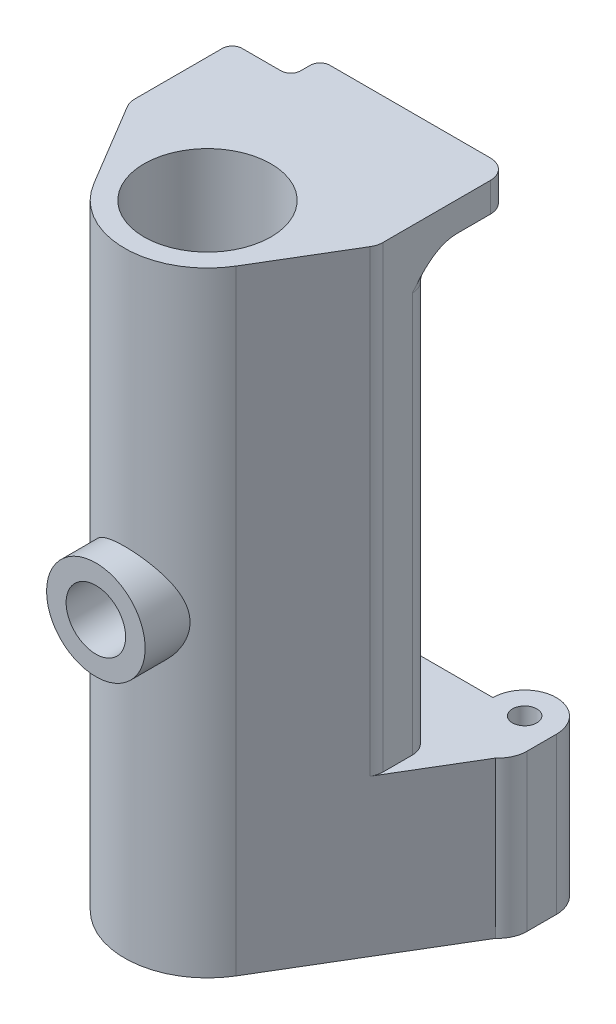
SolidWorks part; units mm, degrees
material "PLA (20%–30% infill + wall)"
ref_plane "Front Plane" through (0, 0, 0) normal (0, 0, 1) x (1, 0, 0)
ref_plane "Top Plane" through (0, 0, 0) normal (0, 1, 0) x (1, 0, 0)
ref_plane "Right Plane" through (0, 0, 0) normal (1, 0, 0) x (0, 0, -1)
sketch "Sketch1" plane through (0, 0, 0) normal (0, 1, 0) x (1, 0, 0)
  line L0 (0, 0) -> (-15, 0) construction
  line L1 (0, 0) -> (0, 18.8352) construction
  line L2 (-11.75, 0) -> (11.75, 0)
  line L3 (-18.25, 0) -> (-18.25, -6)
  line L4 (-18.25, -6) -> (18.25, -6)
  line L5 (18.25, -6) -> (18.25, 0)
  circle A0 centre (-15, 0) radius 1.25
  circle A1 centre (15, 0) radius 1.25
  circle A2 centre (-15, 0) radius 3.25
  circle A3 centre (15, 0) radius 3.25
  dimension "D1" = 30
  dimension "D2" = 2.5
  dimension "D4" = 6
  dimension "D3" = 2
extrude "Boss-Extrude1" add sketch "Sketch1" along normal blind 16 contours A2 A0 | L5 A3 L2 A2 L3 L4 | A3 A1 region at (-15, 0, 3.1581) region at (0, 0, 3.2894) region at (15, 0, -3.1581)
fillet "Fillet1" radius 3 2 edges at (18.25, 8, 6) (-18.25, 8, 6)
sketch "Sketch2" plane through (0, 0, 0) normal (0, -1, 0) x (-1, 0, 0)
  line L0 (0, -6) -> (0, -12.5349) construction
  line L1 (15.25, -6) -> (-15.25, -6) construction
  line L2 (-17.246, -5.2396) -> (-7.2931, -21.8658)
  line L3 (-15.25, -6) -> (15.25, -6)
  line L4 (17.246, -5.2396) -> (7.2931, -21.8658)
  circle A0 centre (0, -17.5) radius 6.5
  arc A1 (-7.2931, -21.8658) -> (7.2931, -21.8658) centre (0, -17.5) ccw
  arc A2 (15.25, -6) -> (18.25, -3) centre (15.25, -3) ccw construction
  arc A3 (-18.25, -3) -> (-15.25, -6) centre (-15.25, -3) ccw construction
  arc A4 (15.25, -6) -> (17.246, -5.2396) centre (15.25, -3) ccw
  arc A5 (-17.246, -5.2396) -> (-15.25, -6) centre (-15.25, -3) ccw
  circle A6 centre (0, -17.5) radius 8.5 construction
  circle M5 centre (15, 0) radius 1.25
  line M6 (-18.25, 0) -> (-18.25, -3)
  arc M7 (-18.25, -3) -> (-15.25, -6) centre (-15.25, -3) ccw
  line M8 (-15.25, -6) -> (15.25, -6)
  arc M9 (15.25, -6) -> (18.25, -3) centre (15.25, -3) ccw
  line M10 (18.25, -3) -> (18.25, 0)
  arc M11 (18.25, 0) -> (11.75, 0) centre (15, 0) ccw
  line M12 (11.75, 0) -> (-11.75, 0)
  arc M13 (-11.75, 0) -> (-18.25, 0) centre (-15, 0) ccw
  circle M14 centre (-15, 0) radius 1.25
  dimension "D1" = 13
  dimension "D3" = 11.5
  dimension "D2" = 2
extrude "Boss-Extrude3" add sketch "Sketch2" against normal blind 10 contours L2 A1 L4 L3 A0 M9 M8 M7 | L3 M13 M6 M7 M8 M9 M10 M11 M12 M14 M5 region at (16.4613, 0, 6.1797) region at (0, 0, 2.4765)
sketch "Sketch3" plane through (0, 10, 0) normal (0, 1, 0) x (1, 0, 0)
  line L2 (-17.246, -5.2396) -> (-7.2931, -21.8658) construction
  line L12 (17.246, -5.2396) -> (7.2931, -21.8658) construction
  line L13 (14.2529, -10.2396) -> (7.2931, -21.8658)
  line L14 (-14.2529, -10.2396) -> (-7.2931, -21.8658)
  line L20 (-14.2529, -10.2396) -> (14.2529, -10.2396)
  line L21 (-15.25, -6) -> (15.25, -6) construction
  circle A1 centre (0, -17.5) radius 6.5 construction
  arc A13 (-7.2931, -21.8658) -> (7.2931, -21.8658) centre (0, -17.5) ccw construction
  circle A15 centre (0, -17.5) radius 6.5
  arc A16 (-7.2931, -21.8658) -> (7.2931, -21.8658) centre (0, -17.5) ccw
  dimension "D1" = 4.2396
extrude "Boss-Extrude4" add sketch "Sketch3" along normal blind 53
fillet "Fillet3" radius 2 2 edges at (14.2529, 36.5, 10.2396) (-14.2529, 36.5, 10.2396)
ref_plane "Plane1" through (0, 0, 18.2396) normal (0, 0, -1) x (-1, 0, 0)
sketch "Sketch4" plane through (0, 0, 18.2396) normal (0, 0, -1) x (-1, 0, 0)
  line L0 (0, 0) -> (0, 63) construction
  line L1 (7.2931, 63) -> (-7.2931, 63) construction
  circle A0 centre (0, 31.5) radius 3.05
  dimension "D1" = 6.1
extrude "Cut-Extrude1" cut sketch "Sketch4" against normal through all
ref_plane "Plane2" through (0, 0, 25.9396) normal (0, 0, -1) x (-1, 0, 0)
sketch "Sketch6" plane through (0, 0, 25.9396) normal (0, 0, -1) x (-1, 0, 0)
  circle A0 centre (0, 31.5) radius 3.05 construction
  circle A1 centre (0, 31.5) radius 3.05
  circle A2 centre (0, 31.5) radius 5.05
  dimension "D1" = 2
extrude "Boss-Extrude5" add sketch "Sketch6" along normal up to surface and the other way blind 3 up to face at (-0.4906, 34.5103, 25.9858)
sketch "Sketch7" plane through (0, 10, 0) normal (0, 1, 0) x (1, 0, 0)
  line L4 (-10.7246, -10.2396) -> (10.7246, -10.2396)
  line L5 (12.4407, -13.2669) -> (17.246, -5.2396)
  line L6 (15.25, -6) -> (-15.25, -6)
  line L7 (-17.246, -5.2396) -> (-12.4407, -13.2669)
  line L8 (-10.7246, -10.2396) -> (10.7246, -10.2396)
  line L9 (12.4407, -13.2669) -> (17.246, -5.2396)
  line L10 (15.25, -6) -> (-15.25, -6)
  line L11 (-17.246, -5.2396) -> (-12.4407, -13.2669)
  arc A4 (12.4407, -13.2669) -> (10.7246, -10.2396) centre (10.7246, -12.2396) ccw
  arc A5 (15.25, -6) -> (17.246, -5.2396) centre (15.25, -3) ccw
  arc A6 (-17.246, -5.2396) -> (-15.25, -6) centre (-15.25, -3) ccw
  arc A7 (-10.7246, -10.2396) -> (-12.4407, -13.2669) centre (-10.7246, -12.2396) ccw
  arc A8 (12.4407, -13.2669) -> (10.7246, -10.2396) centre (10.7246, -12.2396) ccw
  arc A9 (15.25, -6) -> (17.246, -5.2396) centre (15.25, -3) ccw
  arc A10 (-17.246, -5.2396) -> (-15.25, -6) centre (-15.25, -3) ccw
  arc A11 (-10.7246, -10.2396) -> (-12.4407, -13.2669) centre (-10.7246, -12.2396) ccw
  dimension "D1" = 0
extrude "Boss-Extrude6" add sketch "Sketch7" along normal up to surface (6 mm away) up to face at (-15, 16, 1.25)
sketch "Sketch8" plane through (0, 63, 0) normal (0, 1, 0) x (1, 0, 0)
  line L0 (10.7246, -10.2396) -> (-10.7246, -10.2396) construction
  line L1 (10.7246, -10.2396) -> (-10.7246, -10.2396)
  line L2 (-10.7246, 0.7604) -> (10.7246, 0.7604)
  line L3 (-12.7246, -12.2396) -> (-12.7246, 0.7604)
  line L4 (-12.7246, 0.7604) -> (-10.7246, 0.7604)
  line L5 (12.7246, -12.2396) -> (12.7246, 0.7604)
  line L6 (12.7246, 0.7604) -> (10.7246, 0.7604)
  arc A0 (-10.7246, -10.2396) -> (-12.4407, -13.2669) centre (-10.7246, -12.2396) ccw construction
  arc A1 (-10.7246, -10.2396) -> (-12.4407, -13.2669) centre (-10.7246, -12.2396) ccw construction
  arc A2 (12.4407, -13.2669) -> (10.7246, -10.2396) centre (10.7246, -12.2396) ccw construction
  arc A3 (12.4407, -13.2669) -> (10.7246, -10.2396) centre (10.7246, -12.2396) ccw construction
  arc A4 (12.7246, -12.2396) -> (10.7246, -10.2396) centre (10.7246, -12.2396) ccw
  arc A5 (-10.7246, -10.2396) -> (-12.7246, -12.2396) centre (-10.7246, -12.2396) ccw
  dimension "D1" = 11
extrude "Boss-Extrude7" add sketch "Sketch8" against normal blind 3
fillet "Fillet5" radius 2 2 edges at (-12.7246, 61.5, -0.7604) (12.7246, 61.5, -0.7604)
fillet "Fillet6" radius 3 3 edges at (-12.1389, 60, 10.8254) (12.1389, 60, 10.8254) (0, 60, 10.2396)
sketch "Sketch9" plane through (0, 16, 0) normal (0, 1, 0) x (1, 0, 0)
  line L0 (0, -10.2396) -> (0, 0) construction
  line L1 (-10.7246, -10.2396) -> (10.7246, -10.2396) construction
  line L2 (-11.75, 0) -> (11.75, 0) construction
  line L3 (10.9578, -10.2396) -> (10.9578, -10.2533)
  line L4 (10.9578, -10.2396) -> (-10.9578, -10.2396)
  line L6 (10.9578, -7.2396) -> (-10.9578, -7.2396)
  line L8 (-10.9578, -10.2396) -> (-10.9578, -10.2533)
  line L9 (12.7246, -12.2396) -> (12.7246, -7.2396)
  line L10 (12.7246, -7.2396) -> (10.9578, -7.2396)
  line L11 (-12.7246, -12.2396) -> (-12.7246, -7.2396)
  line L12 (-12.7246, -7.2396) -> (-10.9578, -7.2396)
  arc A0 (12.7246, -12.2396) -> (10.7246, -10.2396) centre (10.7246, -12.2396) ccw
  arc A1 (12.4407, -13.2669) -> (10.7246, -10.2396) centre (10.7246, -12.2396) ccw construction
  arc A2 (-10.7246, -10.2396) -> (-12.4407, -13.2669) centre (-10.7246, -12.2396) ccw construction
  arc A3 (10.9578, -10.2533) -> (10.7246, -10.2396) centre (10.7246, -12.2396) ccw
  arc A4 (-10.7246, -10.2396) -> (-10.9578, -10.2533) centre (-10.7246, -12.2396) ccw
  arc A5 (-10.7246, -10.2396) -> (-12.7246, -12.2396) centre (-10.7246, -12.2396) ccw
  point P10 (0, -10.2396)
  arc M7 (-12.4407, -13.2669) -> (-10.7246, -10.2396) centre (-10.7246, -12.2396) cw
  line M8 (-10.7246, -10.2396) -> (10.7246, -10.2396)
  arc M9 (10.7246, -10.2396) -> (12.4407, -13.2669) centre (10.7246, -12.2396) cw
  dimension "D2" = 3
extrude "Boss-Extrude8" add sketch "Sketch9" along normal up to surface (44 mm away) contours L0 L6 L4 M8 | L0 L4 L6 | L3 L4 M9 | L4 L8 M7 region at (-6.4923, 16, 8.7824) region at (6.4923, 16, 8.7824) region at (10.8996, 16, 10.2437) region at (-10.8996, 16, 10.2437) up to face at (0, 60, 3.7146)
fillet "Fillet7" radius 2 2 edges at (-12.7246, 38, 7.2396) (12.7246, 38, 7.2396)
fillet "Fillet10" radius 3 3 edges at (12.1389, 60, 7.8254) (-12.1389, 60, 7.8254) (0, 60, 7.2396)
sketch "Sketch10" plane through (0, 63, 0) normal (0, 1, 0) x (1, 0, 0)
  line L0 (-12.7246, -2.2396) -> (-6.7246, -2.2396)
  line L1 (-12.7246, -1.2396) -> (-12.7246, -12.2396) construction
  line L2 (-6.7246, -2.2396) -> (-6.7246, 0.7604)
  line L3 (10.7246, 0.7604) -> (-10.7246, 0.7604) construction
  dimension "D1" = 3
  dimension "D2" = 6
extrude "Cut-Extrude3" cut sketch "Sketch10" against normal blind 3 and the other way through all
fillet "Fillet11" radius 1 3 edges at (-12.7246, 61.5, 2.2396) (-6.7246, 61.5, 2.2396) (-6.7246, 61.5, -0.7604)
